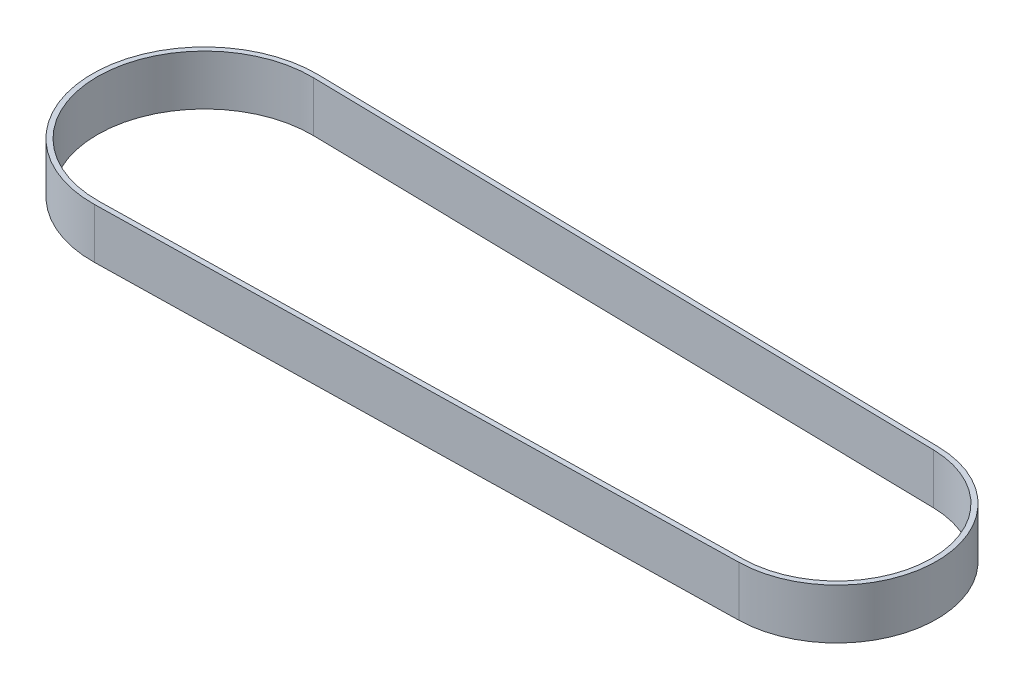
SolidWorks part; units mm, degrees
other "Markup1"
sketch "Sketch2" plane through (-23.4, 0, -23.4) normal (-0.231, -0.9167, -0.326) x (-0.972, 0.232, 0.0366)
material "BUTYL"
ref_plane "Front Plane" through (0, 0, 0) normal (0, 0, 1) x (1, 0, 0)
ref_plane "Top Plane" through (0, 0, 0) normal (0, 1, 0) x (1, 0, 0)
ref_plane "Right Plane" through (0, 0, 0) normal (1, 0, 0) x (0, 0, -1)
sketch "Sketch1" plane through (0, 0, 0) normal (0, 1, 0) x (1, 0, 0)
  line L0 (0, 0) -> (126, 0) construction
  line L1 (0.4151, 21.346) -> (126.3675, 18.8964)
  line L2 (0.4346, 22.3458) -> (126.3869, 19.8962)
  line L3 (0.4346, -22.3458) -> (126.3869, -19.8962)
  line L4 (0.4151, -21.346) -> (126.3675, -18.8964)
  arc A0 (0.4151, 21.346) -> (0.4151, -21.346) centre (0, 0) ccw
  arc A1 (126.3675, -18.8964) -> (126.3675, 18.8964) centre (126, 0) ccw
  arc A2 (126.3869, -19.8962) -> (126.3869, 19.8962) centre (126, 0) ccw
  arc A3 (0.4346, 22.3458) -> (0.4346, -22.3458) centre (0, 0) ccw
  dimension "D1" = 42.7
  dimension "D3" = 37.8
  dimension "D2" = 126
  dimension "D4" = 1
extrude "Boss-Extrude1" add sketch "Sketch1" along normal blind 10
